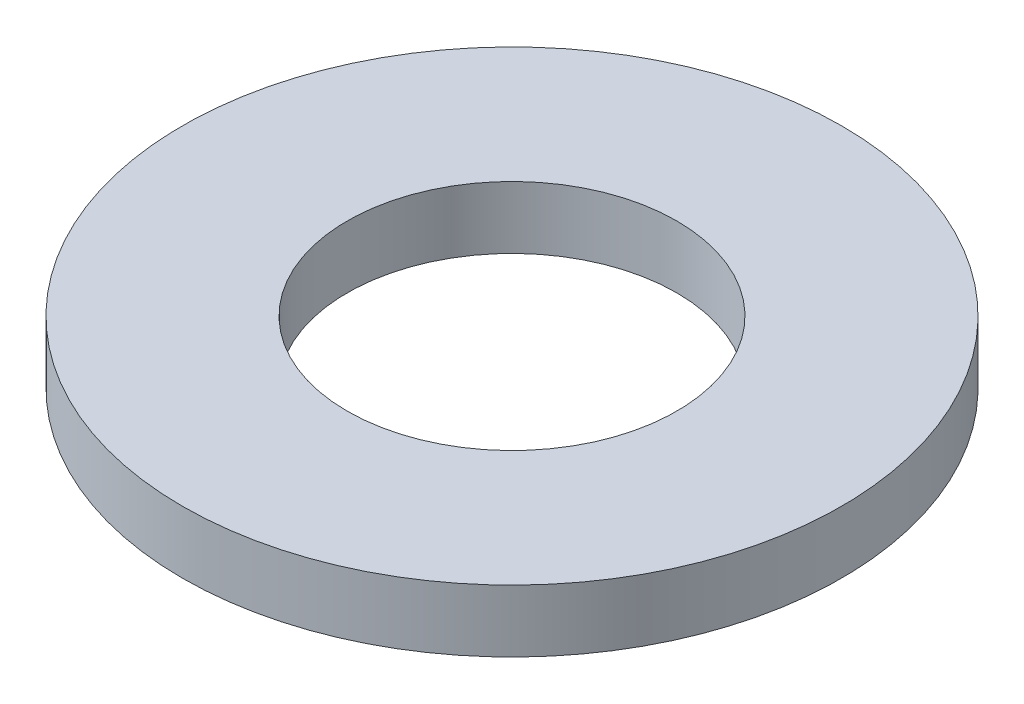
SolidWorks part; units mm, degrees
ref_plane "Front Plane" through (0, 0, 0) normal (0, 0, 1) x (1, 0, 0)
ref_plane "Top Plane" through (0, 0, 0) normal (0, 1, 0) x (1, 0, 0)
ref_plane "Right Plane" through (0, 0, 0) normal (1, 0, 0) x (0, 0, -1)
ref_plane "Plane1" through (0, 0, 0) normal (0, -1, 0) x (1, 0, 0)
sketch "Sketch1" plane through (0, 0, 0) normal (0, -1, 0) x (1, 0, 0)
  circle A0 centre (-47.1143, -64.5518) radius 8.7313
  circle A1 centre (-47.1143, -64.5518) radius 4.3656
extrude "Boss-Extrude1" add sketch "Sketch1" against normal blind 1.651
ref_axis "Axis1" through (-47.1143, 4.472, -64.5518) along (0, -1, 0)
